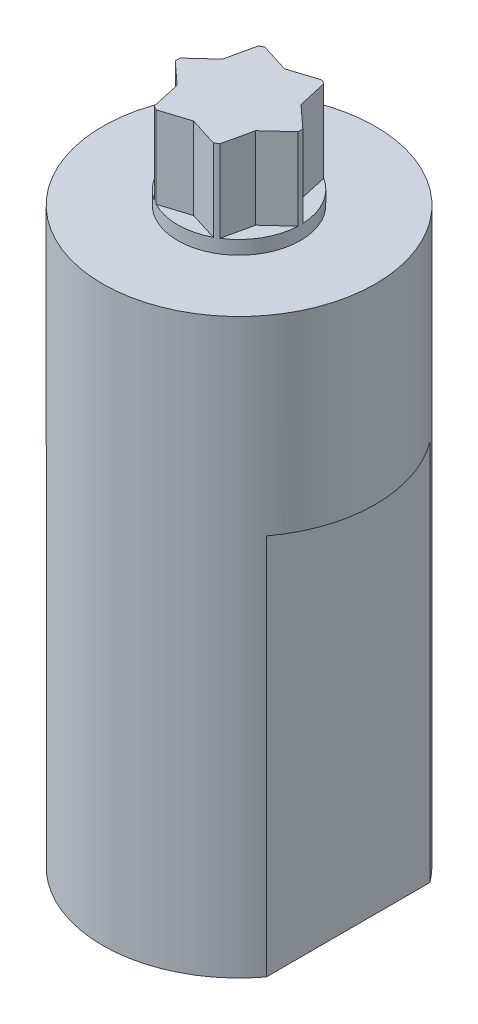
SolidWorks part; units mm, degrees
material "BUTYL"
ref_plane "Front Plane" through (0, 0, 0) normal (0, 0, 1) x (1, 0, 0)
ref_plane "Top Plane" through (0, 0, 0) normal (0, 1, 0) x (1, 0, 0)
ref_plane "Right Plane" through (0, 0, 0) normal (1, 0, 0) x (0, 0, -1)
sketch "Sketch1" plane through (0, 0, 0) normal (0, 1, 0) x (1, 0, 0)
  circle A0 centre (0, 0) radius 5
  dimension "D1" = 10
extrude "Boss-Extrude1" add sketch "Sketch1" along normal blind 7
sketch "Sketch2" plane through (0, 0, 0) normal (0, 1, 0) x (1, 0, 0)
  line L0 (-4, -3) -> (-4, 3)
  line L1 (4, -3) -> (4, 3)
  circle A0 centre (0, 0) radius 5 construction
  arc A1 (-4, -3) -> (4, -3) centre (0, 0) ccw
  arc A2 (4, 3) -> (-4, 3) centre (0, 0) ccw
  dimension "D1" = 8
extrude "Boss-Extrude2" add sketch "Sketch2" against normal blind 14 contours L1 A2 L0 A1 region at (0, 0, 0)
sketch "Sketch3" plane through (0, 7, 0) normal (0, 1, 0) x (1, 0, 0)
  circle A0 centre (0, 0) radius 2.25
  dimension "D1" = 4.5
extrude "Boss-Extrude3" add sketch "Sketch3" along normal blind 3.5
sketch "Sketch4" plane through (0, 10.5, 0) normal (0, 1, 0) x (1, 0, 0)
  line L0 (0, 1.6625) -> (-5.9097, 3.5218)
  line L1 (-5.9097, 3.5218) -> (5.9097, 3.5218)
  line L2 (5.9097, 3.5218) -> (0, 1.6625)
extrude "Cut-Extrude1" cut sketch "Sketch4" against normal blind 3
pattern_circular "CirPattern1" count 6 over 360 about axis through (0, 7, 0) along (0, 1, 0) of "Cut-Extrude1"
